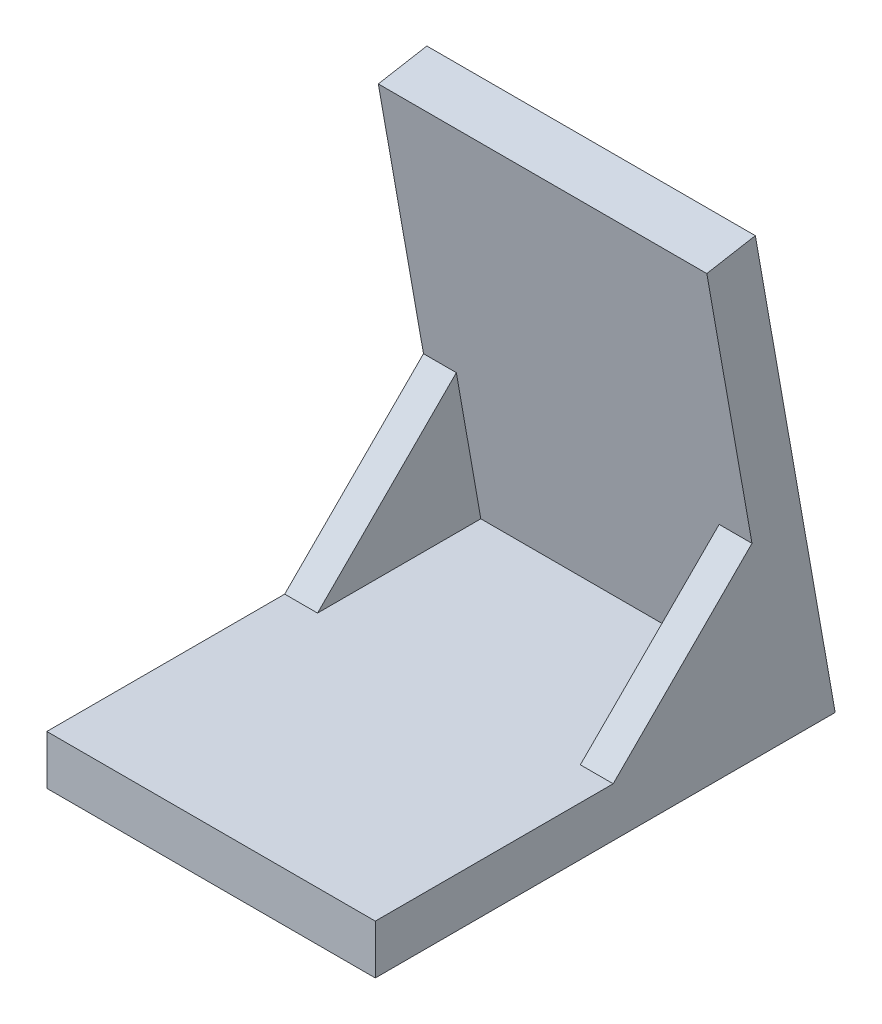
SolidWorks part; units mm, degrees
ref_plane "Front Plane" through (0, 0, 0) normal (0, 0, 1) x (1, 0, 0)
ref_plane "Top Plane" through (0, 0, 0) normal (0, 1, 0) x (1, 0, 0)
ref_plane "Right Plane" through (0, 0, 0) normal (1, 0, 0) x (0, 0, -1)
sketch "Sketch1" plane through (0, 0, 0) normal (1, 0, 0) x (0, 0, -1)
  line L0 (0, 0) -> (140, 0)
  line L1 (140, 0) -> (115.6893, 137.8731)
  line L2 (115.6893, 137.8731) -> (100.9171, 135.2684)
  line L3 (100.9171, 135.2684) -> (122.1237, 15)
  line L4 (122.1237, 15) -> (0, 15)
  line L5 (0, 15) -> (0, 0)
  dimension "D1" = 15
  dimension "D2" = 15
  dimension "D3" = 80
  dimension "D4" = 140
  dimension "D5" = 140
extrude "Boss-Extrude1" add sketch "Sketch1" along normal blind 50 and the other way blind 50
sketch "Sketch3" plane through (-50, 0, 0) normal (-1, 0, 0) x (0, 0, 1)
  line L0 (-114.6729, 57.2555) -> (-72.4175, 15)
  line L1 (-100.9171, 135.2684) -> (-122.1237, 15) construction
  line L2 (-122.1237, 15) -> (0, 15) construction
  dimension "D1" = 45
rib "Rib1" sketch "Sketch3" sketch "Sketch3" thickness 10 extrusion direction parallel to sketch draft on no parameters "D1"=10
mirror "Mirror1" about plane through (0, 0, 0) normal (1, 0, 0) of "Rib1"
